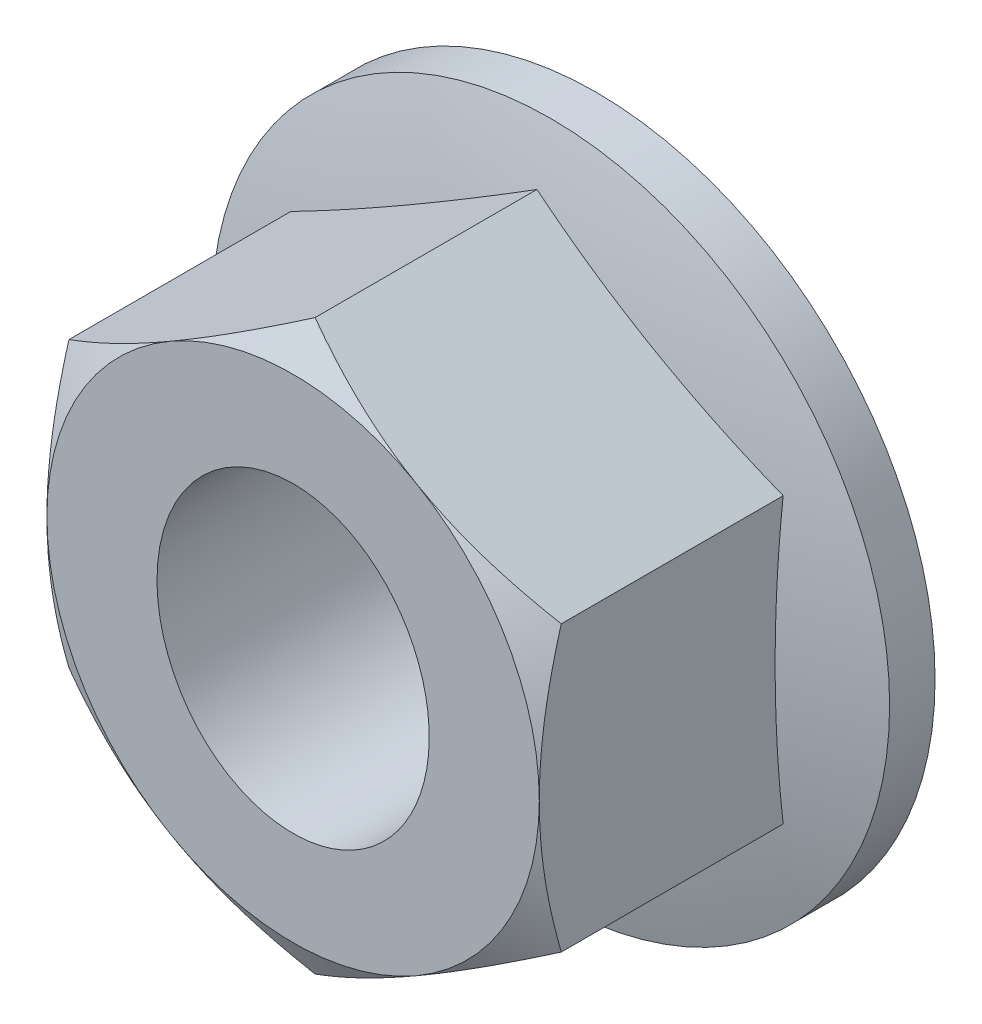
SolidWorks part; units mm, degrees
ref_plane "Front" through (0, 0, 0) normal (0, 0, 1) x (1, 0, 0)
ref_plane "Top" through (0, 0, 0) normal (0, 1, 0) x (1, 0, 0)
ref_plane "Right" through (0, 0, 0) normal (1, 0, 0) x (0, 0, -1)
sketch "Sketch1" plane through (0, 0, 0) normal (0, 0, 1) x (1, 0, 0)
  line L1 (6.5, -3.7528) -> (6.5, 3.7528)
  line L2 (6.5, 3.7528) -> (0, 7.5056)
  line L3 (0, 7.5056) -> (-6.5, 3.7528)
  line L4 (-6.5, 3.7528) -> (-6.5, -3.7528)
  line L5 (-6.5, -3.7528) -> (0, -7.5056)
  line L6 (0, -7.5056) -> (6.5, -3.7528)
  circle A0 centre (0, 0) radius 6.5 construction
  circle A1 centre (0, 0) radius 8.95 construction
  point P10 (0, 8.95)
  dimension "Flange OD" = 17.9
  dimension "Hex" = 13
extrude "Extrude1" add sketch "Sketch1" along normal mid plane 8
sketch "Sketch18" plane through (0, 0, 0) normal (1, 0, 0) x (0, 0, -1)
  line L0 (4, 0) -> (4, 8.95)
  line L1 (4, 8.95) -> (2.8, 8.95)
  line L2 (1.6, 0) -> (4, 0) construction
  line L3 (1.6, 0) -> (1.6, 8.95) construction
  line L4 (4, -3.7528) -> (4, 3.7528) construction
  line L5 (2.8, 8.95) -> (2.8, 0) construction
  line L6 (4, 0) -> (1.6, 0)
  arc A0 (2.8, 8.95) -> (1.6, 0) centre (35.576, 0) ccw
  dimension "Flange Thickness" = 1.2
revolve "Revolve1" add sketch "Sketch18" angle 360 about L6
sketch "Sketch2" plane through (0, 0, 4) normal (0, 0, 1) x (1, 0, 0)
  circle A0 centre (0, 0) radius 6.5 construction
  circle A5 centre (0, 0) radius 6.5
extrude "Cut-Extrude1" cut sketch "Sketch2" against normal through all draft 60 flip side to cut
sketch "Sketch4" plane through (0, 0, -4) normal (0, 0, -1) x (-1, 0, 0)
  line L0 (4, 0) -> (3.5941, 0) construction
  circle A0 centre (0, 0) radius 4
  circle A1 centre (0, 0) radius 3.5941 construction
  dimension "Thread OD" = 8
  dimension "D1" = 0.4059
sketch "Sketch5" plane through (0, 0, 4) normal (0, 0, -1) x (-1, 0, 0)
  circle A2 centre (0, 0) radius 4 construction
  circle A3 centre (0, 0) radius 4
sketch "Sketch7" plane through (0, 0, -4) normal (0, 0, -1) x (-1, 0, 0)
  circle A0 centre (0, 0) radius 4 construction
  circle A1 centre (0, 0) radius 4
curve "Helix/Spiral1" pitch 1.25 height 9.25 turns 7.4 parameters "pitch"=1.25
extrude "Cut-Extrude10" cut sketch "Sketch5" along normal through all
sketch "Sketch16" plane through (0, 0, 4) normal (0, 0, 1) x (1, 0, 0)
  circle A0 centre (0, 0) radius 6.5
  circle A1 centre (0, 0) radius 6.5 construction
  circle A2 centre (0, 0) radius 4 construction
  circle A3 centre (0, 0) radius 3.5941 construction
  ellipse E0 centre (0, 0) end of major axis (0, 4) minor radius 3.5941
extrude "Extrude2" add sketch "Sketch16" against normal up to surface (8 mm away)
sketch "Sketch9" [suppressed] plane through (0, 0, -7.9375) normal (1, 0, 0) x (0, 0, -1)
  line L0 (-3.9375, 4) -> (-2.8438, 4)
  line L1 (-2.8438, 4) -> (-3.3125, 3.1881)
  line L2 (-3.3125, 3.1881) -> (-3.4687, 3.1881)
  line L3 (-3.4687, 3.1881) -> (-3.9375, 4)
  line L4 (-3.3906, 3.1881) -> (-3.3906, 4) construction
  line L5 (-3.7031, 3.5941) -> (-3.0781, 3.5941) construction
  line L6 (-3.9375, -4) -> (-3.9375, 4) construction
  dimension "D1" = 0.625
  dimension "D2" = 0.1562
  dimension "D3" = 60
  dimension "D4" = 0.8119
sweep "Sweep1" [suppressed] add profiles "Sketch9" path "Helix/Spiral1"
sketch "Sketch10" [suppressed] plane through (0, 0, -4) normal (0, 0, -1) x (-1, 0, 0)
  line L6 (-6.5, 3.7528) -> (-6.5, -3.7528)
  line L7 (0, 7.5056) -> (-6.5, 3.7528)
  line L8 (6.5, 3.7528) -> (0, 7.5056)
  line L9 (6.5, -3.7528) -> (6.5, 3.7528)
  line L10 (0, -7.5056) -> (6.5, -3.7528)
  line L11 (-6.5, -3.7528) -> (0, -7.5056)
  line L12 (-6.5, 3.7528) -> (-6.5, -3.7528)
  line L13 (0, 7.5056) -> (-6.5, 3.7528)
  line L14 (6.5, 3.7528) -> (0, 7.5056)
  line L15 (6.5, -3.7528) -> (6.5, 3.7528)
  line L16 (0, -7.5056) -> (6.5, -3.7528)
  line L17 (-6.5, -3.7528) -> (0, -7.5056)
  dimension "D1" = 0
extrude "Cut-Extrude4" [suppressed] cut sketch "Sketch10" along normal through all
sketch "Sketch11" [suppressed] plane through (0, 0, 4) normal (0, 0, 1) x (1, 0, 0)
  line L6 (6.5, -3.7528) -> (6.5, 3.7528)
  line L7 (6.5, 3.7528) -> (0, 7.5056)
  line L8 (0, 7.5056) -> (-6.5, 3.7528)
  line L9 (-6.5, 3.7528) -> (-6.5, -3.7528)
  line L10 (-6.5, -3.7528) -> (0, -7.5056)
  line L11 (0, -7.5056) -> (6.5, -3.7528)
  line L12 (6.5, -3.7528) -> (6.5, 3.7528)
  line L13 (6.5, 3.7528) -> (0, 7.5056)
  line L14 (0, 7.5056) -> (-6.5, 3.7528)
  line L15 (-6.5, 3.7528) -> (-6.5, -3.7528)
  line L16 (-6.5, -3.7528) -> (0, -7.5056)
  line L17 (0, -7.5056) -> (6.5, -3.7528)
  dimension "D1" = 0
extrude "Cut-Extrude5" [suppressed] cut sketch "Sketch11" along normal through all
sketch "Sketch13" [suppressed] plane through (0, 0, 4) normal (0, 0, 1) x (1, 0, 0)
  spline S0 degree 3 poles (-0.2563, -4.0762) (0.2563, -4.0762) (0.5075, -4.0467) (1.0002, -3.9319) (1.2437, -3.845) (1.6991, -3.6237) (1.9138, -3.4891) (2.3168, -3.1735) (2.4988, -2.9975) (2.8277, -2.6124) (2.9752, -2.4012) (3.2263, -1.9609) (3.3311, -1.7309) (3.5006, -1.2517) (3.5646, -1.0034) (3.6491, -0.5054) (3.6703, -0.2536) (3.6702, 0.2559) (3.6485, 0.51) (3.5638, 1.0069) (3.5008, 1.2514) (3.3308, 1.7317) (3.2248, 1.9636) (2.9754, 2.4008) (2.8313, 2.6077) (2.5005, 2.9959) (2.317, 3.1729) (1.9212, 3.4837) (1.7071, 3.6193) (1.2471, 3.8439) (1.0092, 3.929) (0.5179, 4.045) (0.261, 4.0756) (-0.2461, 4.0768) (-0.4974, 4.0485) (-0.9953, 3.9336) (-1.2361, 3.8481) (-1.6921, 3.6277) (-1.9111, 3.4907) (-2.3111, 3.1783) (-2.4938, 3.0028) (-2.826, 2.6148) (-2.9723, 2.4057) (-3.2236, 1.9663) (-3.3302, 1.733) (-3.5002, 1.2532) (-3.5635, 1.0084) (-3.6487, 0.5093) (-3.6703, 0.2527) (-3.6702, -0.2544) (-3.649, -0.5059) (-3.5644, -1.0048) (-3.4998, -1.2543) (-3.3307, -1.7317) (-3.2262, -1.9609) (-2.9759, -2.4) (-2.8281, -2.6118) (-2.4995, -2.9968) (-2.3184, -3.1718) (-1.9205, -3.4843) (-1.7013, -3.6224) (-1.2469, -3.8437) (-1.0094, -3.9292) (-0.5126, -4.0461) (-0.2563, -4.0762) (0.2563, -4.0762) (0.5075, -4.0467) knots -0.03125 -0.03125 0 0 0.03125 0.03125 0.0625 0.0625 0.09375 0.09375 0.125 0.125 0.15625 0.15625 0.1875 0.1875 0.21875 0.21875 0.25 0.25 0.28125 0.28125 0.3125 0.3125 0.34375 0.34375 0.375 0.375 0.40625 0.40625 0.4375 0.4375 0.46875 0.46875 0.5 0.5 0.53125 0.53125 0.5625 0.5625 0.59375 0.59375 0.625 0.625 0.65625 0.65625 0.6875 0.6875 0.71875 0.71875 0.75 0.75 0.78125 0.78125 0.8125 0.8125 0.84375 0.84375 0.875 0.875 0.90625 0.90625 0.9375 0.9375 0.96875 0.96875 1 1 1.03125 1.03125 1.0625 only from (0, -4.0762) to (0, -4.0762)
  spline S1 degree 3 poles (-0.2563, -4.0762) (0.2563, -4.0762) (0.5075, -4.0467) (1.0002, -3.9319) (1.2437, -3.845) (1.6991, -3.6237) (1.9138, -3.4891) (2.3168, -3.1735) (2.4988, -2.9975) (2.8277, -2.6124) (2.9752, -2.4012) (3.2263, -1.9609) (3.3311, -1.7309) (3.5006, -1.2517) (3.5646, -1.0034) (3.6491, -0.5054) (3.6703, -0.2536) (3.6702, 0.2559) (3.6485, 0.51) (3.5638, 1.0069) (3.5008, 1.2514) (3.3308, 1.7317) (3.2248, 1.9636) (2.9754, 2.4008) (2.8313, 2.6077) (2.5005, 2.9959) (2.317, 3.1729) (1.9212, 3.4837) (1.7071, 3.6193) (1.2471, 3.8439) (1.0092, 3.929) (0.5179, 4.045) (0.261, 4.0756) (-0.2461, 4.0768) (-0.4974, 4.0485) (-0.9953, 3.9336) (-1.2361, 3.8481) (-1.6921, 3.6277) (-1.9111, 3.4907) (-2.3111, 3.1783) (-2.4938, 3.0028) (-2.826, 2.6148) (-2.9723, 2.4057) (-3.2236, 1.9663) (-3.3302, 1.733) (-3.5002, 1.2532) (-3.5635, 1.0084) (-3.6487, 0.5093) (-3.6703, 0.2527) (-3.6702, -0.2544) (-3.649, -0.5059) (-3.5644, -1.0048) (-3.4998, -1.2543) (-3.3307, -1.7317) (-3.2262, -1.9609) (-2.9759, -2.4) (-2.8281, -2.6118) (-2.4995, -2.9968) (-2.3184, -3.1718) (-1.9205, -3.4843) (-1.7013, -3.6224) (-1.2469, -3.8437) (-1.0094, -3.9292) (-0.5126, -4.0461) (-0.2563, -4.0762) (0.2563, -4.0762) (0.5075, -4.0467) knots -0.03125 -0.03125 0 0 0.03125 0.03125 0.0625 0.0625 0.09375 0.09375 0.125 0.125 0.15625 0.15625 0.1875 0.1875 0.21875 0.21875 0.25 0.25 0.28125 0.28125 0.3125 0.3125 0.34375 0.34375 0.375 0.375 0.40625 0.40625 0.4375 0.4375 0.46875 0.46875 0.5 0.5 0.53125 0.53125 0.5625 0.5625 0.59375 0.59375 0.625 0.625 0.65625 0.65625 0.6875 0.6875 0.71875 0.71875 0.75 0.75 0.78125 0.78125 0.8125 0.8125 0.84375 0.84375 0.875 0.875 0.90625 0.90625 0.9375 0.9375 0.96875 0.96875 1 1 1.03125 1.03125 1.0625 only from (0, -4.0762) to (0, -4.0762)
  dimension "D1" = 0.0762
extrude "Cut-Extrude8" [suppressed] cut sketch "Sketch13" against normal blind 2.1875 draft 45
sketch "Sketch14" [suppressed] plane through (0, 0, -4) normal (0, 0, -1) x (-1, 0, 0)
  spline S1 degree 3 poles (-0.2563, -4.0762) (0.2563, -4.0762) (0.5126, -4.0461) (1.0094, -3.9292) (1.2469, -3.8437) (1.7013, -3.6224) (1.9205, -3.4843) (2.3184, -3.1718) (2.4995, -2.9968) (2.8281, -2.6118) (2.9759, -2.4) (3.2262, -1.9609) (3.3307, -1.7317) (3.4998, -1.2543) (3.5644, -1.0048) (3.649, -0.5059) (3.6702, -0.2544) (3.6703, 0.2527) (3.6487, 0.5093) (3.5635, 1.0084) (3.5002, 1.2532) (3.3302, 1.733) (3.2236, 1.9663) (2.9723, 2.4057) (2.826, 2.6148) (2.4938, 3.0028) (2.3111, 3.1783) (1.9111, 3.4907) (1.6921, 3.6277) (1.2361, 3.8481) (0.9953, 3.9336) (0.4974, 4.0485) (0.2461, 4.0768) (-0.261, 4.0756) (-0.5179, 4.045) (-1.0092, 3.929) (-1.2471, 3.8439) (-1.7071, 3.6193) (-1.9212, 3.4837) (-2.317, 3.1729) (-2.5005, 2.9959) (-2.8313, 2.6077) (-2.9754, 2.4008) (-3.2248, 1.9636) (-3.3308, 1.7317) (-3.5008, 1.2514) (-3.5638, 1.0069) (-3.6485, 0.51) (-3.6702, 0.2559) (-3.6703, -0.2536) (-3.6491, -0.5054) (-3.5646, -1.0034) (-3.5006, -1.2517) (-3.3311, -1.7309) (-3.2263, -1.9609) (-2.9752, -2.4012) (-2.8277, -2.6124) (-2.4988, -2.9975) (-2.3168, -3.1735) (-1.9138, -3.4891) (-1.6991, -3.6237) (-1.2437, -3.845) (-1.0002, -3.9319) (-0.5075, -4.0467) (-0.2563, -4.0762) (0.2563, -4.0762) (0.5126, -4.0461) knots -0.03125 -0.03125 0 0 0.03125 0.03125 0.0625 0.0625 0.09375 0.09375 0.125 0.125 0.15625 0.15625 0.1875 0.1875 0.21875 0.21875 0.25 0.25 0.28125 0.28125 0.3125 0.3125 0.34375 0.34375 0.375 0.375 0.40625 0.40625 0.4375 0.4375 0.46875 0.46875 0.5 0.5 0.53125 0.53125 0.5625 0.5625 0.59375 0.59375 0.625 0.625 0.65625 0.65625 0.6875 0.6875 0.71875 0.71875 0.75 0.75 0.78125 0.78125 0.8125 0.8125 0.84375 0.84375 0.875 0.875 0.90625 0.90625 0.9375 0.9375 0.96875 0.96875 1 1 1.03125 1.03125 1.0625 only from (0, -4.0762) to (0, -4.0762)
  spline S2 degree 3 poles (-0.2563, -4.0762) (0.2563, -4.0762) (0.5126, -4.0461) (1.0094, -3.9292) (1.2469, -3.8437) (1.7013, -3.6224) (1.9205, -3.4843) (2.3184, -3.1718) (2.4995, -2.9968) (2.8281, -2.6118) (2.9759, -2.4) (3.2262, -1.9609) (3.3307, -1.7317) (3.4998, -1.2543) (3.5644, -1.0048) (3.649, -0.5059) (3.6702, -0.2544) (3.6703, 0.2527) (3.6487, 0.5093) (3.5635, 1.0084) (3.5002, 1.2532) (3.3302, 1.733) (3.2236, 1.9663) (2.9723, 2.4057) (2.826, 2.6148) (2.4938, 3.0028) (2.3111, 3.1783) (1.9111, 3.4907) (1.6921, 3.6277) (1.2361, 3.8481) (0.9953, 3.9336) (0.4974, 4.0485) (0.2461, 4.0768) (-0.261, 4.0756) (-0.5179, 4.045) (-1.0092, 3.929) (-1.2471, 3.8439) (-1.7071, 3.6193) (-1.9212, 3.4837) (-2.317, 3.1729) (-2.5005, 2.9959) (-2.8313, 2.6077) (-2.9754, 2.4008) (-3.2248, 1.9636) (-3.3308, 1.7317) (-3.5008, 1.2514) (-3.5638, 1.0069) (-3.6485, 0.51) (-3.6702, 0.2559) (-3.6703, -0.2536) (-3.6491, -0.5054) (-3.5646, -1.0034) (-3.5006, -1.2517) (-3.3311, -1.7309) (-3.2263, -1.9609) (-2.9752, -2.4012) (-2.8277, -2.6124) (-2.4988, -2.9975) (-2.3168, -3.1735) (-1.9138, -3.4891) (-1.6991, -3.6237) (-1.2437, -3.845) (-1.0002, -3.9319) (-0.5075, -4.0467) (-0.2563, -4.0762) (0.2563, -4.0762) (0.5126, -4.0461) knots -0.03125 -0.03125 0 0 0.03125 0.03125 0.0625 0.0625 0.09375 0.09375 0.125 0.125 0.15625 0.15625 0.1875 0.1875 0.21875 0.21875 0.25 0.25 0.28125 0.28125 0.3125 0.3125 0.34375 0.34375 0.375 0.375 0.40625 0.40625 0.4375 0.4375 0.46875 0.46875 0.5 0.5 0.53125 0.53125 0.5625 0.5625 0.59375 0.59375 0.625 0.625 0.65625 0.65625 0.6875 0.6875 0.71875 0.71875 0.75 0.75 0.78125 0.78125 0.8125 0.8125 0.84375 0.84375 0.875 0.875 0.90625 0.90625 0.9375 0.9375 0.96875 0.96875 1 1 1.03125 1.03125 1.0625 only from (0, -4.0762) to (0, -4.0762)
  dimension "D1" = 0
extrude "Cut-Extrude9" [suppressed] cut sketch "Sketch14" against normal blind 2.1875 draft 45
ref_plane "Contact Plane 1" through (0, 0, -4) normal (0, 0, -1) x (-1, 0, 0)
ref_axis "Center Axis 1" through (0, 0, 50) along (0, 0, -1)
equation "\"D1@Sketch9\" = \"pitch@Helix/Spiral1\"*.5"
equation "\"D2@Sketch9\" = \"pitch@Helix/Spiral1\"*.125"
equation "\"D3@Helix/Spiral1\"=\"height@Extrude1\"+\"pitch@Helix/Spiral1\""
equation "\"D1@Cut-Extrude8\" = \"pitch@Helix/Spiral1\"*1.750"
equation "\"D1@Cut-Extrude9\" = \"D1@Cut-Extrude8\""
equation "\"D1@Sketch4\" = \"D4@Sketch9\"*.5"
